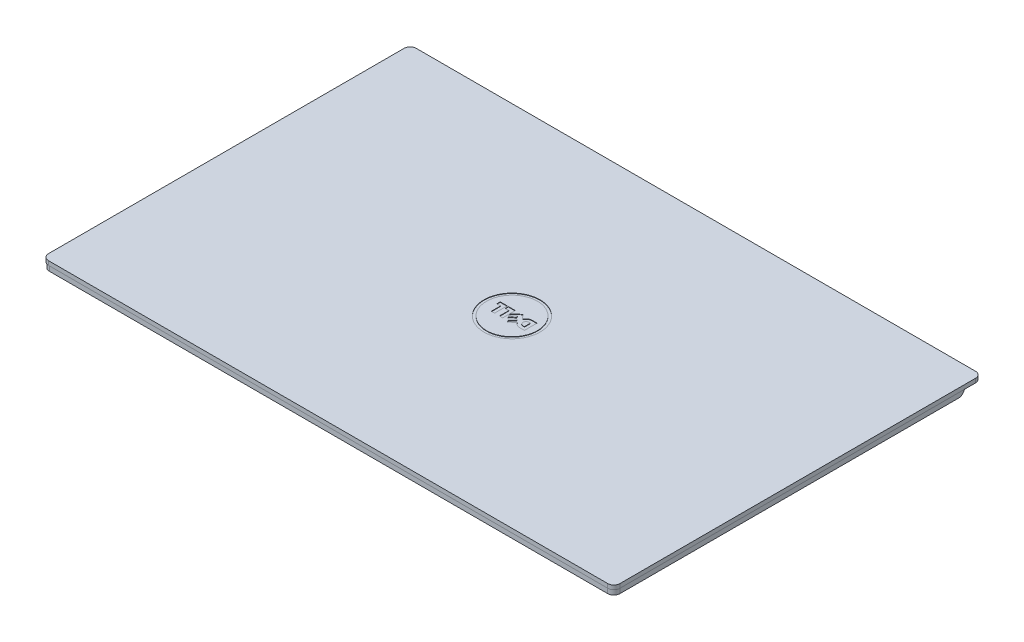
SolidWorks part; units mm, degrees
ref_plane "Front Plane" through (0, 0, 0) normal (0, 0, 1) x (1, 0, 0)
ref_plane "Top Plane" through (0, 0, 0) normal (0, 1, 0) x (1, 0, 0)
ref_plane "Right Plane" through (0, 0, 0) normal (1, 0, 0) x (0, 0, -1)
sketch "Sketch1" plane through (0, 0, 0) normal (1, 0, 0) x (0, 0, -1)
  line L0 (0, 0) -> (0, 3.175)
  line L1 (0, 3.175) -> (228.6762, 3.175)
  line L2 (228.6762, 3.175) -> (228.6762, 0)
  line L3 (228.6762, 0) -> (0, 0)
  dimension "D1" = 3.175
  dimension "D2" = 228.6762
extrude "Boss-Extrude1" add sketch "Sketch1" along normal blind 355.6
sketch "Sketch2" plane through (0, 0, 0) normal (0, -1, 0) x (-1, 0, 0)
  line L0 (0, 218.5162) -> (-31.75, 218.5162)
  line L1 (0, 0) -> (0, 228.6762) construction
  line L2 (-31.75, 218.5162) -> (-31.75, 228.6762)
  line L3 (-355.6, 228.6762) -> (0, 228.6762) construction
  line L4 (-31.75, 228.6762) -> (0, 228.6762)
  line L5 (0, 228.6762) -> (0, 218.5162)
  line L6 (-355.6, 228.6762) -> (-355.6, 218.5162)
  line L7 (-355.6, 0) -> (-355.6, 228.6762) construction
  line L8 (-355.6, 218.5162) -> (-323.85, 218.5162)
  line L9 (-323.85, 218.5162) -> (-323.85, 228.6762)
  line L10 (-323.85, 228.6762) -> (-355.6, 228.6762)
  dimension "D1" = 31.75
  dimension "D2" = 10.16
extrude "Cut-Extrude1" cut sketch "Sketch2" against normal through all
sketch "Sketch3" plane through (0, 0, 0) normal (0, -1, 0) x (1, 0, 0)
  line L0 (5.08, -5.08) -> (5.08, -203.5175)
  line L1 (5.08, -203.5175) -> (350.52, -203.5175)
  line L2 (350.52, -203.5175) -> (350.52, -5.08)
  line L3 (350.52, -5.08) -> (5.08, -5.08)
  line L4 (0, 0) -> (0, -218.5162) construction
  line L5 (355.6, 0) -> (355.6, -218.5162) construction
  line L6 (355.6, 0) -> (0, 0) construction
  dimension "D1" = 5.08
  dimension "D2" = 5.08
  dimension "D3" = 5.08
  dimension "D4" = 198.4375
extrude "Cut-Extrude2" cut sketch "Sketch3" against normal blind 2.032
sketch "Sketch4" plane through (0, 2.032, 0) normal (0, -1, 0) x (1, 0, 0)
  line L0 (5.08, -5.08) -> (5.08, -203.5175)
  line L1 (5.08, -203.5175) -> (350.52, -203.5175)
  line L2 (350.52, -203.5175) -> (350.52, -5.08)
  line L3 (350.52, -5.08) -> (5.08, -5.08)
extrude "Boss-Extrude2" add sketch "Sketch4" along normal blind 2.0066
sketch "Sketch6" plane through (0, 3.175, 0) normal (0, 1, 0) x (1, 0, 0)
  line L6 (-0.254, 218.5162) -> (-0.254, 228.9302)
  line L7 (-0.254, 228.9302) -> (355.854, 228.9302)
  line L8 (355.854, 228.9302) -> (355.854, 218.5162)
  line L9 (355.854, 218.5162) -> (355.854, -0.254)
  line L10 (355.854, -0.254) -> (-0.254, -0.254)
  line L11 (-0.254, -0.254) -> (-0.254, 218.5162)
  line L12 (355.854, 218.5162) -> (355.854, -0.254)
  line L13 (355.854, -0.254) -> (-0.254, -0.254)
  line L14 (-0.254, -0.254) -> (-0.254, 218.5162)
  line L15 (323.85, 228.6762) -> (31.75, 228.6762) construction
  dimension "D2" = 0.254
  dimension "D1" = 0.254
extrude "Boss-Extrude3" add sketch "Sketch6" along normal blind 2.54
fillet "Fillet1" radius 3.81 6 edges at (0, 1.5875, 0) (-0.254, 4.445, 0.254) (-0.254, 4.445, -228.9302) (355.854, 4.445, -228.9302) (355.6, 1.5875, 0) (355.854, 4.445, 0.254)
sketch "Sketch7" plane through (0, 5.715, 0) normal (0, 1, 0) x (1, 0, 0)
  line L0 (177.8, -0.254) -> (177.8, 228.9302) construction
  line L1 (3.556, -0.254) -> (352.044, -0.254) construction
  line L2 (352.044, 228.9302) -> (3.556, 228.9302) construction
  line L3 (355.854, 114.3381) -> (-0.254, 114.3381) construction
  line L4 (355.854, 3.556) -> (355.854, 225.1202) construction
  line L5 (-0.254, 225.1202) -> (-0.254, 3.556) construction
  circle A0 centre (177.8, 114.3381) radius 17.4625
  circle A1 centre (177.8, 114.3381) radius 15.875
  dimension "D1" = 34.925
  dimension "D2" = 1.5875
extrude "Cut-Extrude3" cut sketch "Sketch7" against normal blind 0.254
sketch "Sketch8" plane through (0, 5.715, 0) normal (0, 1, 0) x (1, 0, 0)
  line L0 (187.4394, 112.4331) -> (187.4394, 116.2431)
  line L1 (187.4394, 116.2431) -> (186.5504, 116.2431)
  line L2 (187.4394, 112.4331) -> (186.5504, 112.4331)
  line L3 (189.4714, 110.4011) -> (186.5504, 110.4011)
  line L4 (189.4714, 118.2751) -> (186.5504, 118.2751)
  line L5 (189.4714, 110.4011) -> (189.4714, 118.2751)
  line L6 (193.675, 114.3381) -> (184.6454, 114.3381) construction
  line L7 (182.8822, 115.7679) -> (180.3799, 118.6248)
  line L8 (180.3799, 118.6248) -> (175.9433, 114.7388)
  line L10 (176.5291, 113.3836) -> (179.4738, 115.9628)
  line L11 (179.4738, 115.9628) -> (180.1767, 115.1603)
  line L12 (180.1767, 115.1603) -> (177.232, 112.5811)
  line L13 (177.232, 112.5811) -> (178.1581, 111.5239)
  line L14 (178.1581, 111.5239) -> (181.1027, 114.1031)
  line L15 (181.1027, 114.1031) -> (181.8056, 113.3006)
  line L16 (181.8056, 113.3006) -> (178.861, 110.7214)
  line L17 (178.861, 110.7214) -> (179.787, 109.6641)
  line L18 (179.787, 109.6641) -> (183.055, 112.5265)
  line L19 (175.9433, 114.7388) -> (175.9433, 118.2751)
  line L20 (175.9433, 110.4011) -> (175.9433, 114.0525)
  line L21 (175.9433, 118.2751) -> (171.6253, 118.2751)
  line L22 (171.6253, 118.2751) -> (171.6253, 116.2431)
  line L23 (171.6253, 116.2431) -> (173.9113, 116.2431)
  line L24 (173.9113, 116.2431) -> (173.9113, 110.4011)
  line L25 (173.9113, 110.4011) -> (175.9433, 110.4011)
  line L26 (168.8313, 116.2431) -> (168.8313, 110.4011)
  line L27 (168.8313, 110.4011) -> (170.8633, 110.4011)
  line L28 (170.8633, 110.4011) -> (170.8633, 118.2751)
  line L29 (170.8633, 118.2751) -> (166.5453, 118.2751)
  line L30 (166.5453, 116.2431) -> (168.8313, 116.2431)
  line L31 (166.5453, 118.2751) -> (166.5453, 116.2431)
  line L32 (177.8, 98.4631) -> (177.8, 130.2131) construction
  line L33 (182.6134, 114.3381) -> (177.6189, 114.3381) construction
  line L34 (173.9113, 114.3381) -> (161.925, 114.3381) construction
  line L35 (175.9433, 114.0525) -> (176.5291, 113.3836)
  arc A0 (186.5504, 112.4331) -> (186.5504, 116.2431) centre (186.5504, 114.3381) cw
  arc A1 (186.5504, 110.4011) -> (183.055, 112.5265) centre (186.5504, 114.3381) cw
  circle A2 centre (177.8, 114.3381) radius 15.875 construction
  circle A3 centre (177.8, 114.3381) radius 15.875 construction
  arc A4 (182.8822, 115.7679) -> (186.5504, 118.2751) centre (186.5504, 114.3381) cw
  arc A5 (186.5504, 110.4011) -> (186.5504, 118.2751) centre (186.5504, 114.3381) cw construction
  dimension "D2" = 0.889
  dimension "D1" = 3.81
  dimension "D4" = 48.785
  dimension "D5" = 6.35
  dimension "D6" = 1.0668
  dimension "D7" = 2.032
  dimension "D8" = 2.286
  dimension "D9" = 7.874
  dimension "D11" = 11.6714
  dimension "D12" = 6.5892
  dimension "D13" = 0.3497
  dimension "D14" = 2.4355
  dimension "D15" = 3.9145
  dimension "D16" = 3.5305
  dimension "D17" = 3.048
  dimension "D18" = 3.9145
  dimension "D19" = 1.4055
  dimension "D3" = 2.032
  dimension "D10" = 2
extrude "Cut-Extrude4" cut sketch "Sketch8" against normal blind 0.254
sketch "Sketch9" plane through (0, 0, 0) normal (0, -1, 0) x (1, 0, 0)
  line L0 (0, -218.5162) -> (0, -3.81) construction
  line L1 (5.08, -203.5175) -> (350.52, -203.5175) construction
  line L2 (177.8, 0) -> (177.8, -228.6762) construction
  line L3 (351.79, 0) -> (3.81, 0) construction
  line L4 (323.85, -228.6762) -> (31.75, -228.6762) construction
  line L5 (143.0013, -209.6135) -> (208.4668, -209.6135) construction
  line L7 (163.5975, -204.7875) -> (163.5975, -214.4395)
  line L8 (163.5975, -204.7875) -> (167.1535, -204.7875)
  line L9 (163.5975, -214.4395) -> (167.1535, -214.4395)
  line L10 (166.3915, -211.6455) -> (167.1535, -211.6455)
  line L11 (166.3915, -207.5815) -> (166.3915, -211.6455)
  line L12 (166.3915, -207.5815) -> (167.1535, -207.5815)
  line L13 (171.7477, -211.0911) -> (177.4351, -215.3221)
  line L14 (177.4351, -215.3221) -> (181.4359, -209.9442)
  line L15 (181.4359, -209.2348) -> (180.4637, -208.5116)
  line L16 (180.4637, -208.5116) -> (177.2929, -212.7739)
  line L17 (177.2929, -212.7739) -> (176.396, -212.1066)
  line L18 (176.396, -212.1066) -> (179.5668, -207.8443)
  line L19 (179.5668, -207.8443) -> (178.1177, -206.7663)
  line L20 (178.1177, -206.7663) -> (174.9469, -211.0286)
  line L21 (174.9469, -211.0286) -> (174.05, -210.3613)
  line L22 (174.05, -210.3613) -> (177.2208, -206.0991)
  line L23 (177.2208, -206.0991) -> (175.7717, -205.021)
  line L24 (175.7717, -205.021) -> (171.9484, -210.1604)
  line L25 (181.4359, -204.7875) -> (181.4359, -209.2348)
  line L26 (181.4359, -214.4395) -> (187.0236, -214.4395)
  line L27 (187.0236, -214.4395) -> (187.0236, -211.8852)
  line L28 (187.0236, -211.8852) -> (184.0748, -211.8852)
  line L29 (184.0748, -211.8852) -> (184.0748, -204.7875)
  line L30 (184.0748, -204.7875) -> (181.4359, -204.7875)
  line L31 (181.4359, -209.9442) -> (181.4359, -214.4395)
  line L32 (190.6788, -204.7875) -> (188.0399, -204.7875)
  line L34 (188.0399, -204.7875) -> (188.0399, -209.2348)
  line L35 (188.0399, -209.9442) -> (188.0399, -214.4395)
  line L36 (188.0399, -214.4395) -> (193.6276, -214.4395)
  line L37 (193.6276, -214.4395) -> (193.6276, -211.8852)
  line L38 (193.6276, -211.8852) -> (190.6788, -211.8852)
  line L39 (190.6788, -211.8852) -> (190.6788, -204.7875)
  line L40 (188.0399, -209.2348) -> (188.0399, -209.9442)
  circle A0 centre (96.52, -212.4075) radius 1.905
  arc A1 (167.1535, -204.7875) -> (171.9484, -210.1604) centre (167.1535, -209.6135) cw
  arc A2 (167.1535, -207.5815) -> (167.1535, -211.6455) centre (167.1535, -209.6135) cw
  arc A3 (171.7477, -211.0911) -> (167.1535, -214.4395) centre (167.1535, -209.6135) cw
  arc A4 (167.1535, -204.7875) -> (167.1535, -214.4395) centre (167.1535, -209.6135) cw construction
  dimension "D1" = 3.81
  dimension "D7" = 36.647
  dimension "D2" = 96.52
  dimension "D3" = 8.89
  dimension "D4" = 9.652
  dimension "D5" = 3.556
  dimension "D8" = 10.4525
  dimension "D9" = 7.0886
  dimension "D10" = 6.4056
  dimension "D11" = 1.1179
  dimension "D12" = 1.8061
  dimension "D13" = 14.2025
  dimension "D14" = 5.3124
  dimension "D15" = 0.8826
  dimension "D16" = 4.4473
  dimension "D17" = 2.6389
  dimension "D18" = 2.9488
  dimension "D19" = 2.5543
  dimension "D21" = 1.0163
  dimension "D22" = 6.096
  dimension "D6" = 2.794
  dimension "D20" = 2
extrude "Cut-Extrude5" cut sketch "Sketch9" against normal blind 0.254
sketch "Sketch10" plane through (0, 0.254, 0) normal (0, -1, 0) x (1, 0, 0)
  circle A0 centre (96.52, -212.4075) radius 1.905
  circle A1 centre (96.52, -212.4075) radius 1.905 construction
extrude "Boss-Extrude4" add sketch "Sketch10" along normal blind 0.2286
sketch "Sketch12" plane through (0, 0.254, 0) normal (0, -1, 0) x (1, 0, 0)
  line L0 (188.0399, -204.7875) -> (188.0399, -214.4395) construction
  line L1 (188.0399, -214.4395) -> (193.6276, -214.4395) construction
  line L2 (193.6276, -214.4395) -> (193.6276, -211.8852) construction
  line L3 (193.6276, -211.8852) -> (190.6788, -211.8852) construction
  line L4 (190.6788, -211.8852) -> (190.6788, -204.7875) construction
  line L5 (190.6788, -204.7875) -> (188.0399, -204.7875) construction
  line L6 (167.1535, -204.7875) -> (163.5975, -204.7875) construction
  line L7 (163.5975, -204.7875) -> (163.5975, -214.4395) construction
  line L8 (163.5975, -214.4395) -> (167.1535, -214.4395) construction
  line L9 (171.7477, -211.0911) -> (177.4351, -215.3221) construction
  line L10 (177.4351, -215.3221) -> (181.4359, -209.9442) construction
  line L11 (181.4359, -209.9442) -> (181.4359, -214.4395) construction
  line L12 (181.4359, -214.4395) -> (187.0236, -214.4395) construction
  line L13 (187.0236, -214.4395) -> (187.0236, -211.8852) construction
  line L14 (187.0236, -211.8852) -> (184.0748, -211.8852) construction
  line L15 (184.0748, -211.8852) -> (184.0748, -204.7875) construction
  line L16 (184.0748, -204.7875) -> (181.4359, -204.7875) construction
  line L17 (181.4359, -204.7875) -> (181.4359, -209.2348) construction
  line L18 (181.4359, -209.2348) -> (180.4637, -208.5116) construction
  line L19 (180.4637, -208.5116) -> (177.2929, -212.7739) construction
  line L20 (177.2929, -212.7739) -> (176.396, -212.1066) construction
  line L21 (176.396, -212.1066) -> (179.5668, -207.8443) construction
  line L22 (179.5668, -207.8443) -> (178.1177, -206.7663) construction
  line L23 (178.1177, -206.7663) -> (174.9469, -211.0286) construction
  line L24 (174.9469, -211.0286) -> (174.05, -210.3613) construction
  line L25 (174.05, -210.3613) -> (177.2208, -206.0991) construction
  line L26 (177.2208, -206.0991) -> (175.7717, -205.021) construction
  line L27 (175.7717, -205.021) -> (171.9484, -210.1604) construction
  line L28 (188.0399, -204.7875) -> (188.0399, -214.4395)
  line L29 (188.0399, -214.4395) -> (193.6276, -214.4395)
  line L30 (193.6276, -214.4395) -> (193.6276, -211.8852)
  line L31 (193.6276, -211.8852) -> (190.6788, -211.8852)
  line L32 (190.6788, -211.8852) -> (190.6788, -204.7875)
  line L33 (190.6788, -204.7875) -> (188.0399, -204.7875)
  line L34 (167.1535, -204.7875) -> (163.5975, -204.7875)
  line L35 (163.5975, -204.7875) -> (163.5975, -214.4395)
  line L36 (163.5975, -214.4395) -> (167.1535, -214.4395)
  line L37 (171.7477, -211.0911) -> (177.4351, -215.3221)
  line L38 (177.4351, -215.3221) -> (181.4359, -209.9442)
  line L39 (181.4359, -209.9442) -> (181.4359, -214.4395)
  line L40 (181.4359, -214.4395) -> (187.0236, -214.4395)
  line L41 (187.0236, -214.4395) -> (187.0236, -211.8852)
  line L42 (187.0236, -211.8852) -> (184.0748, -211.8852)
  line L43 (184.0748, -211.8852) -> (184.0748, -204.7875)
  line L44 (184.0748, -204.7875) -> (181.4359, -204.7875)
  line L45 (181.4359, -204.7875) -> (181.4359, -209.2348)
  line L46 (181.4359, -209.2348) -> (180.4637, -208.5116)
  line L47 (180.4637, -208.5116) -> (177.2929, -212.7739)
  line L48 (177.2929, -212.7739) -> (176.396, -212.1066)
  line L49 (176.396, -212.1066) -> (179.5668, -207.8443)
  line L50 (179.5668, -207.8443) -> (178.1177, -206.7663)
  line L51 (178.1177, -206.7663) -> (174.9469, -211.0286)
  line L52 (174.9469, -211.0286) -> (174.05, -210.3613)
  line L53 (174.05, -210.3613) -> (177.2208, -206.0991)
  line L54 (177.2208, -206.0991) -> (175.7717, -205.021)
  line L55 (175.7717, -205.021) -> (171.9484, -210.1604)
  arc A0 (167.1535, -214.4395) -> (171.7477, -211.0911) centre (167.1535, -209.6135) ccw construction
  arc A1 (171.9484, -210.1604) -> (167.1535, -204.7875) centre (167.1535, -209.6135) ccw construction
  arc A2 (167.1535, -214.4395) -> (171.7477, -211.0911) centre (167.1535, -209.6135) ccw
  arc A3 (171.9484, -210.1604) -> (167.1535, -204.7875) centre (167.1535, -209.6135) ccw
extrude "Boss-Extrude5" add sketch "Sketch12" along normal blind 0.2286
ref_plane "Plane1" through (177.8, 0, 0) normal (-1, 0, 0) x (0, 0, 1)
sketch "Sketch13" plane through (177.8, 0, 0) normal (-1, 0, 0) x (0, 0, 1)
  line L0 (-227.1291, -5.461) -> (-227.1291, 0)
  line L2 (-3.81, 0) -> (-218.5162, 0) construction
  line L3 (-228.6762, 0) -> (-218.5162, 0) construction
  line L4 (-220.1441, 0) -> (-220.1441, -5.461)
  line L5 (-228.6762, 3.175) -> (-228.6762, 0) construction
  line L6 (-227.1291, 0) -> (-220.1441, 0)
  arc A0 (-227.1291, -5.461) -> (-220.1441, -5.461) centre (-223.6366, -5.461) ccw
  circle A1 centre (-223.5962, -5.08) radius 1.905
  dimension "D1" = 3.81
  dimension "D4" = 5.461
  dimension "D2" = 6.985
  dimension "D3" = 5.08
extrude "Boss-Extrude6" add sketch "Sketch13" along normal mid plane 292.1
fillet "Fillet2" radius 3.81 2 edges at (339.725, 0, -218.5162) (15.875, 0, -218.5162)
